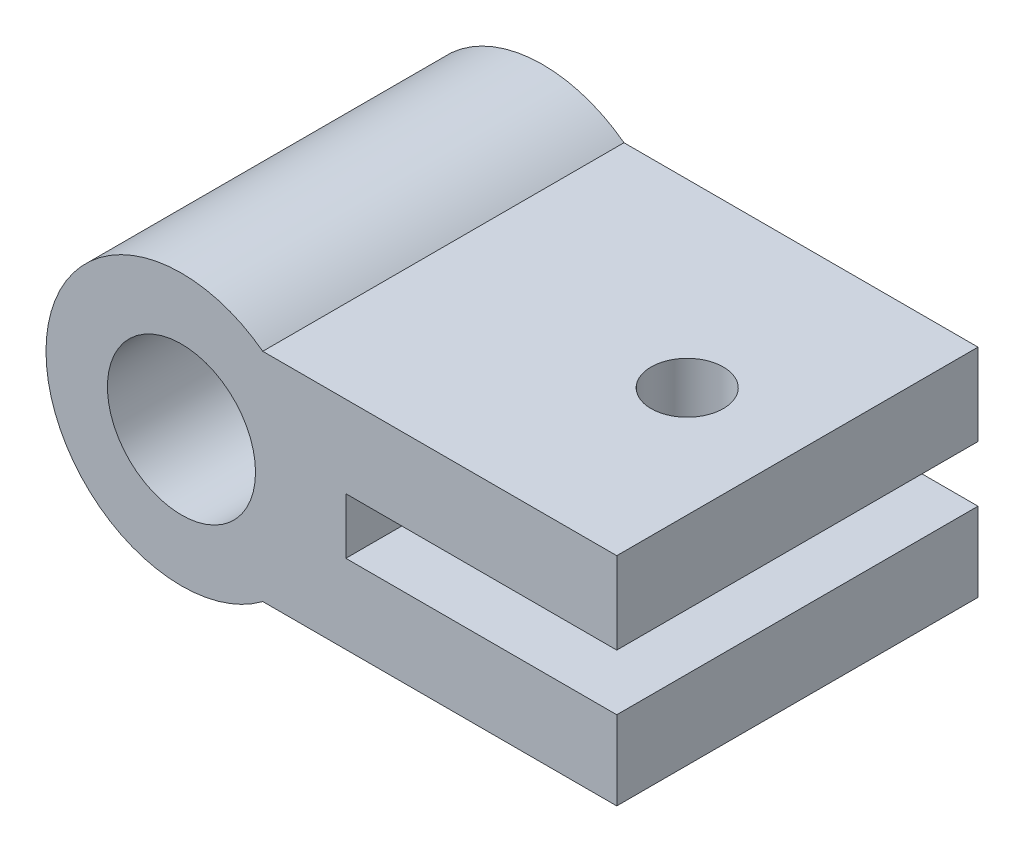
SolidWorks part; units mm, degrees
material "黄铜"
ref_plane "前视基准面" through (0, 0, 0) normal (0, 0, 1) x (1, 0, 0)
ref_plane "上视基准面" through (0, 0, 0) normal (0, 1, 0) x (1, 0, 0)
ref_plane "右视基准面" through (0, 0, 0) normal (1, 0, 0) x (0, 0, -1)
sketch "草图1" plane through (0, 0, 0) normal (0, 0, 1) x (1, 0, 0)
  circle A0 centre (0, 0) radius 7.5
  circle A1 centre (0, 0) radius 4.1
  dimension "D1" = 8.2
  dimension "D2" = 15
extrude "凸台-拉伸1" add sketch "草图1" along normal blind 20
sketch "草图2" plane through (0, 0, 0) normal (0, 1, 0) x (1, 0, 0)
  line L1 (4.1, 0) -> (24.1, 0)
  line L2 (4.1, 0) -> (4.1, -20)
  line L3 (4.1, -20) -> (24.1, -20)
  line L4 (24.1, 0) -> (24.1, -20)
  circle A0 centre (18, -10) radius 2
  point P7 (17.2884, -7.4138)
  point P8 (24.1, -10)
  dimension "D3" = 4
  dimension "D4" = 18
  dimension "D1" = 20
  dimension "D2" = 0
  dimension "D5" = 20
extrude "凸台-拉伸2" add sketch "草图2" along normal blind 6 and the other way blind 6
sketch "草图3" plane through (24.1, 0, 0) normal (1, 0, 0) x (0, 0, -1)
  line L0 (-20, -6) -> (-20, 6) construction
  line L1 (-20, 1.4729) -> (0, 1.4729)
  line L2 (-20, 1.4729) -> (-20, -1.6271)
  line L3 (-20, -1.6271) -> (0, -1.6271)
  line L4 (0, 1.4729) -> (0, -1.6271)
  line L5 (0, -6) -> (0, 6) construction
  dimension "D1" = 3.1
extrude "切除-拉伸1" cut sketch "草图3" against normal blind 15
